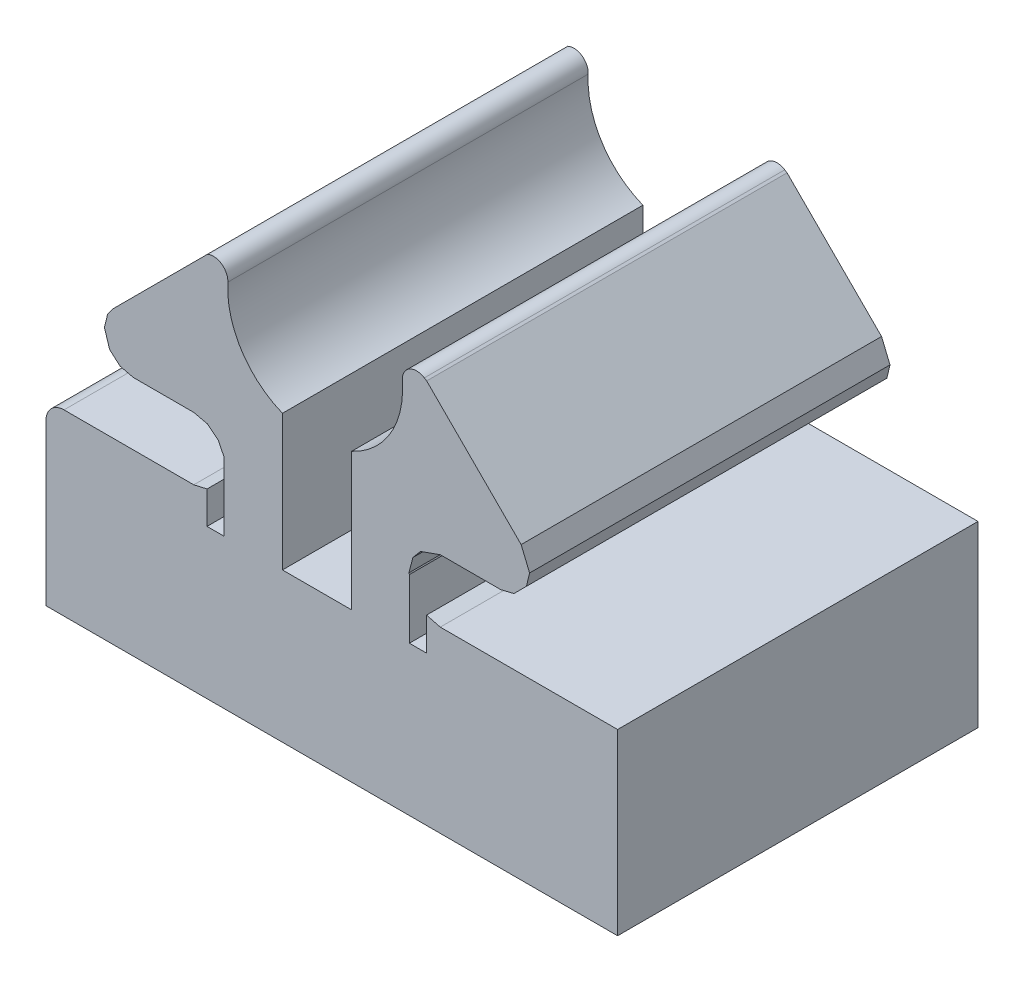
SolidWorks part; units mm, degrees
ref_plane "Front Plane" through (0, 0, 0) normal (0, 0, 1) x (1, 0, 0)
ref_plane "Top Plane" through (0, 0, 0) normal (0, 1, 0) x (1, 0, 0)
ref_plane "Right Plane" through (0, 0, 0) normal (1, 0, 0) x (0, 0, -1)
sketch "Sketch5" plane through (0, 0, 0) normal (0, 0, 1) x (1, 0, 0)
  line L0 (-6.4748, -10.4902) -> (-6.9383, -10.3783)
  line L1 (-6.9383, -10.3783) -> (-7.3088, -10.0545)
  line L2 (-7.3088, -10.0545) -> (-7.4908, -9.4742)
  line L3 (-7.4908, -9.4742) -> (-7.3789, -9.0107)
  line L4 (-7.3789, -9.0107) -> (-7.1932, -8.7558)
  line L5 (-7.1932, -8.7558) -> (-3.8632, -5.4257)
  line L6 (-3.8632, -5.4257) -> (-2.8331, -4.7375)
  line L7 (-2.8331, -4.7375) -> (-1.6181, -4.4958)
  line L8 (-1.6181, -4.4958) -> (1.6181, -4.4958)
  line L9 (1.6181, -4.4958) -> (2.6682, -4.6745)
  line L10 (2.6682, -4.6745) -> (3.8632, -5.4257)
  line L11 (3.8632, -5.4257) -> (7.1932, -8.7558)
  line L12 (7.1932, -8.7558) -> (7.4908, -9.4742)
  line L13 (7.4908, -9.4742) -> (7.3789, -9.9377)
  line L14 (6.4748, -10.4902) -> (6.9383, -10.3783)
  line L15 (6.9383, -10.3783) -> (7.3789, -9.9377)
  line L16 (6.4748, -10.4902) -> (4.3434, -10.4902)
  line L19 (-6.4748, -10.4902) -> (-4.3434, -10.4902)
  line L20 (-4.3434, -10.4902) -> (-3.8632, -10.6)
  line L21 (-3.8632, -10.6) -> (-3.486, -10.8982)
  line L22 (-3.486, -10.8982) -> (-3.2711, -11.3288)
  line L23 (-3.2711, -11.3288) -> (-3.2711, -11.8614)
  line L24 (-3.2711, -11.8614) -> (-3.486, -12.292)
  line L25 (-3.486, -12.292) -> (-3.8632, -12.5902)
  line L26 (-3.8632, -12.5902) -> (-4.3434, -12.7)
  line L27 (-4.3434, -12.7) -> (-9.5504, -12.7)
  line L28 (-9.5504, -12.7) -> (-9.5504, -18.9956)
  line L29 (-9.5504, -18.9956) -> (10.5918, -18.9956)
  line L30 (10.5918, -18.9956) -> (10.5918, -12.7)
  line L31 (10.5918, -12.7) -> (4.3434, -12.7)
  line L32 (4.3434, -12.7) -> (3.8076, -12.5614)
  line L33 (3.8076, -12.5614) -> (3.486, -12.292)
  line L34 (3.486, -12.292) -> (3.2385, -11.5951)
  line L35 (3.2385, -11.5951) -> (3.3771, -11.0593)
  line L36 (3.3771, -11.0593) -> (3.6465, -10.7377)
  line L37 (3.6465, -10.7377) -> (4.3434, -10.4902)
extrude "Boss-Extrude1" add sketch "Sketch5" against normal blind 12.7
sketch "Sketch10" plane through (0, 0, 0) normal (0, 0, 1) x (1, 0, 0)
  circle A0 centre (-0.0665, -6.096) radius 3.0821
extrude "Cut-Extrude1" cut sketch "Sketch10" against normal through all
sketch "Sketch11" plane through (0, 0, 0) normal (0, 0, 1) x (1, 0, 0)
  line L1 (-1.2179, -5.8277) -> (1.2179, -5.8277)
  line L2 (-1.2179, -5.8277) -> (-1.2179, -13.7361)
  line L3 (-1.2179, -13.7361) -> (1.2179, -13.7361)
  line L4 (1.2179, -5.8277) -> (1.2179, -13.7361)
  line L5 (-1.2179, -5.8277) -> (1.2179, -13.7361) construction
  line L6 (-1.2179, -13.7361) -> (1.2179, -5.8277) construction
  point P0 (0, -9.7819)
extrude "Cut-Extrude2" cut sketch "Sketch11" against normal through all
fillet "Fillet1" radius 0.635 1 edges at (-9.5504, -12.7, -6.35)
fillet "Fillet3" radius 0.508 2 edges at (2.6682, -4.6745, -6.35) (-2.8331, -4.7375, -6.35)
sketch "Sketch17" plane through (0, 0, 0) normal (0, 0, 1) x (1, 0, 0)
  line L0 (3.486, -12.292) -> (3.2385, -11.5951) construction
  line L1 (3.2547, -11.6407) -> (3.8597, -11.6407)
  line L2 (3.2547, -11.6407) -> (3.2547, -13.7361)
  line L3 (3.2547, -13.7361) -> (3.8597, -13.7361)
  line L4 (3.8597, -11.6407) -> (3.8597, -13.7361)
  line L5 (-3.2711, -11.3288) -> (-3.2711, -11.8614) construction
  line L6 (-3.2711, -11.5951) -> (-3.8755, -11.5951)
  line L7 (-3.2711, -11.5951) -> (-3.2711, -13.7361)
  line L8 (-3.2711, -13.7361) -> (-3.8755, -13.7361)
  line L9 (-3.8755, -11.5951) -> (-3.8755, -13.7361)
extrude "Cut-Extrude7" cut sketch "Sketch17" against normal through all
sketch "Sketch18" plane through (0, -18.9956, 0) normal (0, -1, 0) x (1, 0, 0)
  line L0 (-9.5504, 0) -> (10.5918, 0) construction
  line L1 (-9.5504, -12.7) -> (-9.5504, 0) construction
  circle A0 centre (0, -6.35) radius 5.08
  dimension "D1" = 10.16
  dimension "D2" = 6.35
  dimension "D3" = 9.5504
extrude "Cut-Extrude8" cut sketch "Sketch18" against normal blind 2.794 contours A0
